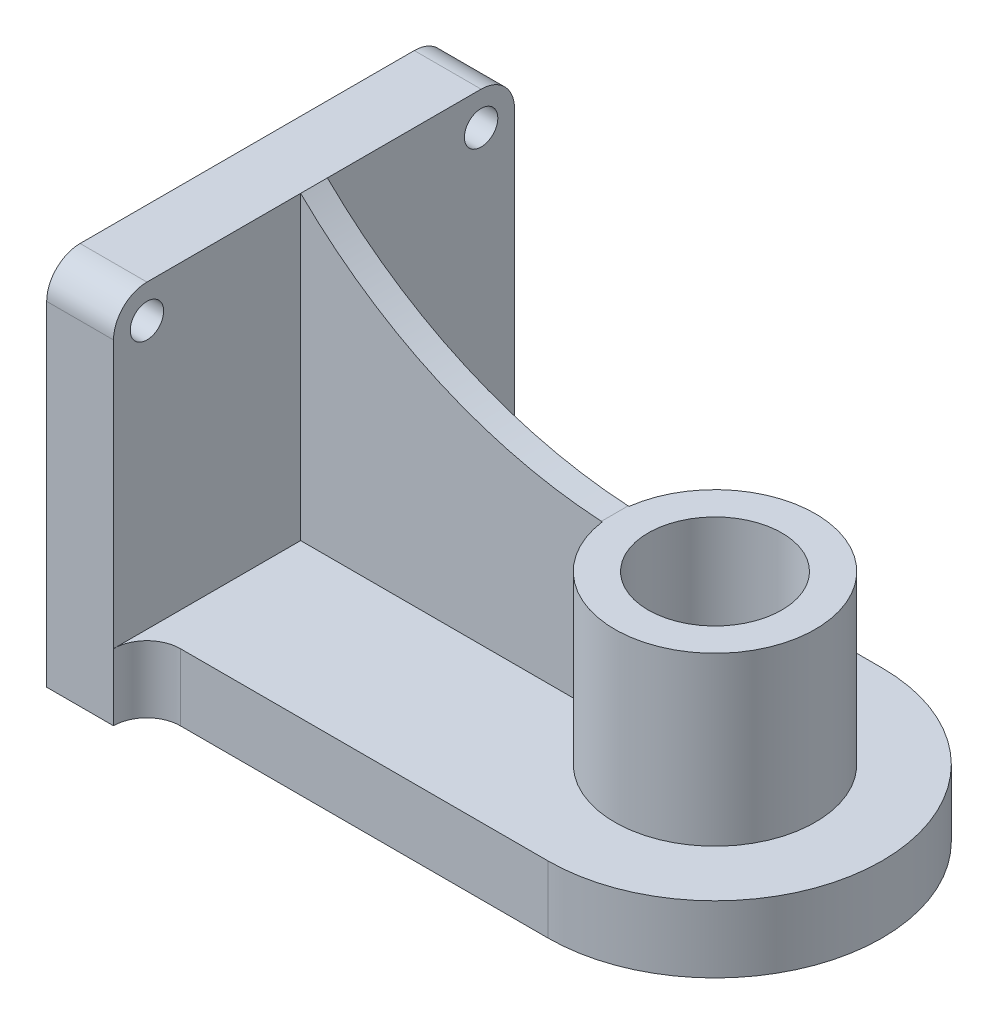
SolidWorks part; units mm, degrees
ref_plane "Front Plane" through (0, 0, 0) normal (0, 0, 1) x (1, 0, 0)
ref_plane "Top Plane" through (0, 0, 0) normal (0, 1, 0) x (1, 0, 0)
ref_plane "Right Plane" through (0, 0, 0) normal (1, 0, 0) x (0, 0, -1)
sketch "Sketch1" plane through (0, 0, 0) normal (0, 0, 1) x (1, 0, 0)
  line L1 (-5, 27.5) -> (5, 27.5)
  line L2 (-5, 27.5) -> (-5, -27.5)
  line L3 (-5, -27.5) -> (5, -27.5)
  line L4 (5, 27.5) -> (5, -27.5)
  line L5 (-5, 27.5) -> (5, -27.5) construction
  line L6 (-5, -27.5) -> (5, 27.5) construction
  point P0 (0, 0)
  dimension "D1" = 10
  dimension "D2" = 55
extrude "Boss-Extrude1" add sketch "Sketch1" along normal mid plane 60
sketch "Sketch2" plane through (0, 0, 0) normal (0, 1, 0) x (1, 0, 0)
  line L0 (65, 25) -> (3, 25)
  line L1 (3, 25) -> (3, -25)
  line L2 (3, -25) -> (65, -25)
  line L3 (5, -30) -> (5, 30) construction
  arc A0 (65, -25) -> (65, 25) centre (65, 0) ccw
  dimension "D1" = 50
  dimension "D2" = 60
  dimension "D3" = 2
extrude "Boss-Extrude2" add sketch "Sketch2" along normal blind 10 from offset 27.5 offset against normal yes
fillet "Fillet3" radius 5 1 edges at (5, -22.5, 25)
fillet "Fillet4" radius 5 1 edges at (5, -22.5, -25)
sketch "Sketch3" plane through (0, -17.5, 0) normal (0, 1, 0) x (1, 0, 0)
  circle A0 centre (65, 0) radius 15
  dimension "D1" = 30
extrude "Boss-Extrude3" add sketch "Sketch3" along normal blind 25
hole_wizard "Hole1" positions "Sketch4" profile "Sketch5" legacy end condition up to next
sketch "Sketch4" plane through (0, 7.5, 0) normal (0, 1, 0) x (1, 0, 0)
  point P0 (65, 0)
sketch "Sketch5" plane through (65, 7.5, 0) normal (1, 0, 0) x (0, 0, 1)
  line L0 (0, 0) -> (0, 35)
  line L1 (0, 35) -> (10, 35)
  line L2 (10, 35) -> (10, 0)
  line L3 (10, 0) -> (0, 0)
  line L4 (0, 110) -> (0, -10) construction
  dimension "Diameter" = 20
  dimension "Depth" = 35
fillet "Fillet5" radius 5 2 edges at (0, 27.5, -30) (0, 27.5, 30)
hole_wizard "Hole2" positions "Sketch8" profile "Sketch7" legacy end condition up to next
sketch "Sketch8" plane through (5, 0, 0) normal (1, 0, 0) x (0, 0, -1)
  point P0 (-25, 22.5)
  point P3 (25, 22.5)
sketch "Sketch7" plane through (5, 22.5, 25) normal (0, 1, 0) x (0, 0, -1)
  line L0 (0, 0) -> (0, 10)
  line L1 (0, 10) -> (2.5, 10)
  line L2 (2.5, 10) -> (2.5, 0)
  line L3 (2.5, 0) -> (0, 0)
  line L4 (0, 110) -> (0, -10) construction
  dimension "Diameter" = 5
  dimension "Depth" = 10
sketch "Sketch9" plane through (0, 0, 0) normal (0, 0, 1) x (1, 0, 0)
  line L0 (51.5, 7.5) -> (51.5, -17.5)
  line L1 (10, -17.5) -> (5, -17.5) construction
  line L2 (10, -17.5) -> (65, -17.5) construction
  line L4 (10, -17.5) -> (5, -17.5)
  line L5 (10, -17.5) -> (51.5, -17.5)
  line L6 (5, 27.5) -> (3, 27.5)
  line L7 (-5, 27.5) -> (5, 27.5) construction
  line L8 (3, 27.5) -> (3, -17.5)
  line L9 (3, -17.5) -> (5, -17.5)
  line L11 (50, 7.5) -> (51.5, 7.5)
  line L12 (80, 7.5) -> (50, 7.5) construction
  line L13 (50, 7.5) -> (50, -17.5) construction
  arc A0 (5, 27.5) -> (50, 7.5) centre (54.1129, 77.3791) ccw
  dimension "D1" = 70
  dimension "D2" = 2
  dimension "D3" = 1.5
extrude "Boss-Extrude7" add sketch "Sketch9" along normal mid plane 4
